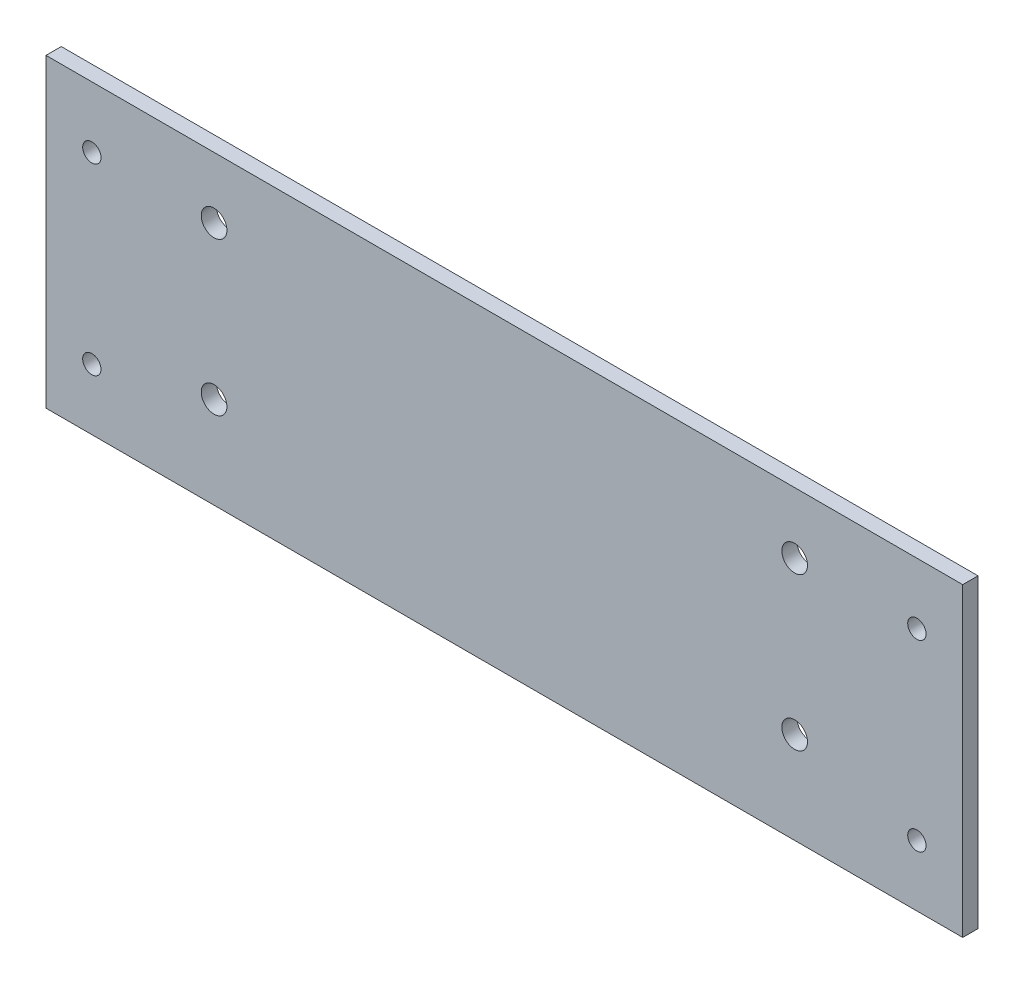
SolidWorks part; units mm, degrees
ref_plane "前视基准面" through (0, 0, 0) normal (0, 0, 1) x (1, 0, 0)
ref_plane "上视基准面" through (0, 0, 0) normal (0, 1, 0) x (1, 0, 0)
ref_plane "右视基准面" through (0, 0, 0) normal (1, 0, 0) x (0, 0, -1)
sketch "Sketch1" plane through (0, 0, 0) normal (0, 0, 1) x (1, 0, 0)
  line L1 (-94.2259, 44.0673) -> (55.7741, 44.0673)
  line L2 (-94.2259, 44.0673) -> (-94.2259, -5.9327)
  line L3 (-94.2259, -5.9327) -> (55.7741, -5.9327)
  line L4 (55.7741, 44.0673) -> (55.7741, -5.9327)
  dimension "D1" = 150
  dimension "D2" = 50
extrude "Boss-Extrude1" add sketch "Sketch1" along normal blind 2.5
sketch "Sketch2" plane through (0, 0, 2.5) normal (0, 0, 1) x (1, 0, 0)
  line L0 (-94.2259, 44.0673) -> (-94.2259, -5.9327) construction
  line L1 (55.7741, -5.9327) -> (55.7741, 44.0673) construction
  line L2 (55.7741, 44.0673) -> (-94.2259, 44.0673) construction
  line L3 (-94.2259, -5.9327) -> (55.7741, -5.9327) construction
  circle A0 centre (-86.7259, 34.0673) radius 1.5
  circle A1 centre (-86.7259, 4.0673) radius 1.5
  circle A2 centre (48.2741, 34.0673) radius 1.5
  circle A3 centre (48.2741, 4.0673) radius 1.5
  dimension "D1" = 3
  dimension "D2" = 3
  dimension "D3" = 3
  dimension "D4" = 3
  dimension "D5" = 7.5
  dimension "D6" = 7.5
  dimension "D8" = 7.5
  dimension "D9" = 10
  dimension "D10" = 10
  dimension "D11" = 10
  dimension "D12" = 10
  dimension "D7" = 7.5
extrude "Cut-Extrude1" cut sketch "Sketch2" against normal through all
sketch "Sketch3" plane through (0, 0, 2.5) normal (0, 0, 1) x (1, 0, 0)
  line L0 (55.7741, 44.0673) -> (-94.2259, 44.0673) construction
  line L1 (-94.2259, 44.0673) -> (-94.2259, -5.9327) construction
  circle A0 centre (-66.7259, 34.0673) radius 2.1
  circle A1 centre (28.2741, 34.0673) radius 2.1
  circle A2 centre (28.2741, 9.0673) radius 2.1
  circle A3 centre (-66.7259, 9.0673) radius 2.1
  dimension "D1" = 4.2
  dimension "D2" = 25
  dimension "D3" = 95
  dimension "D4" = 95
  dimension "D5" = 25
  dimension "D6" = 4.2
  dimension "D7" = 4.2
  dimension "D8" = 4.2
  dimension "D9" = 10
  dimension "D10" = 27.5
extrude "Cut-Extrude2" cut sketch "Sketch3" against normal through all
